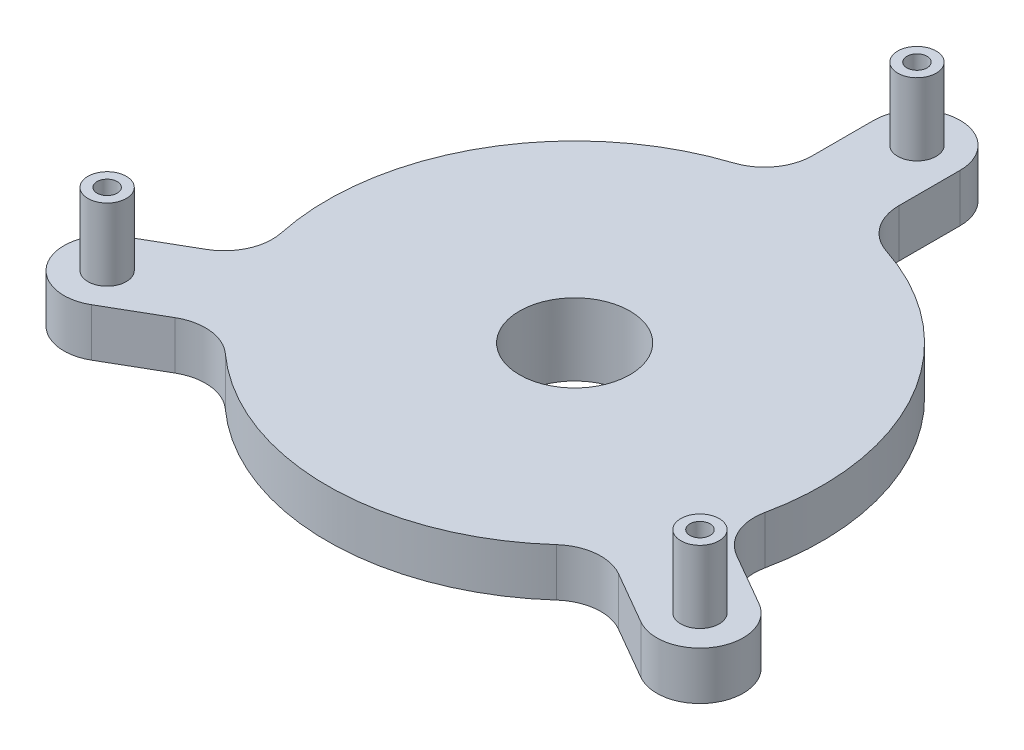
SolidWorks part; units mm, degrees
ref_plane "前基準面" through (0, 0, 0) normal (0, 0, 1) x (1, 0, 0)
ref_plane "上基準面" through (0, 0, 0) normal (0, 1, 0) x (1, 0, 0)
ref_plane "右基準面" through (0, 0, 0) normal (1, 0, 0) x (0, 0, -1)
sketch "草圖1" plane through (0, 0, 0) normal (0, 1, 0) x (1, 0, 0)
  circle A0 centre (0, 0) radius 82.5
  circle A1 centre (0, 0) radius 11.5
  dimension "D1" = 165
  dimension "D2" = 23
extrude "填料-伸長1" add sketch "草圖1" along normal blind 5
sketch "草圖2" plane through (0, 5, 0) normal (0, 1, 0) x (1, 0, 0)
  line L0 (0, 0) -> (0, 82.5) construction
  line L1 (0, 0) -> (71.4471, -41.25) construction
  line L2 (0, 0) -> (-71.4471, -41.25) construction
  circle A0 centre (0, 0) radius 82.5 construction
  circle A1 centre (0, 71.25) radius 4
  circle A2 centre (61.7043, -35.625) radius 4
  circle A3 centre (-61.7043, -35.625) radius 4
  circle A4 centre (0, 71.25) radius 2.1
  circle A5 centre (61.7043, -35.625) radius 2.1
  circle A6 centre (-61.7043, -35.625) radius 2.1
  point P15 (0, 0)
  point P22 (0, 0)
  dimension "D1" = 8
  dimension "D6" = 4.2
  dimension "D2" = 3
  dimension "D3" = 71.25
  dimension "D4" = 1.9
  dimension "D5" = 3
extrude "填料-伸長2" add sketch "草圖2" along normal blind 15
sketch "草圖3" plane through (0, 0, 0) normal (0, -1, 0) x (1, 0, 0)
  circle A0 centre (0, 0) radius 11.5 construction
  circle A1 centre (0, 0) radius 11.5
  circle A2 centre (0, 0) radius 34
  dimension "D2" = 68
  dimension "D1" = 22.5
extrude "填料-伸長3" add sketch "草圖3" along normal blind 5
sketch "草圖4" plane through (0, 5, 0) normal (0, 1, 0) x (1, 0, 0)
  line L0 (-9, 71.25) -> (-9, 58.4915)
  line L1 (9, 71.25) -> (9, 58.4915)
  line L2 (66.2043, -27.8308) -> (55.1551, -21.4515)
  line L3 (57.2043, -43.4192) -> (46.1551, -37.04)
  line L4 (-57.2043, -43.4192) -> (-46.1551, -37.04)
  line L5 (-66.2043, -27.8308) -> (-55.1551, -21.4515)
  circle A0 centre (0, 0) radius 51.5 construction
  arc A1 (-15.9106, 48.9806) -> (-50.3738, -10.7114) centre (0, 0) ccw
  circle A2 centre (-61.7043, -35.625) radius 9
  arc A3 (-66.2043, -27.8308) -> (-57.2043, -43.4192) centre (-61.7043, -35.625) ccw
  arc A4 (50.3738, -10.7114) -> (15.9106, 48.9806) centre (0, 0) ccw
  arc A5 (-46.1551, -37.04) -> (-34.4632, -38.2693) centre (-41.1551, -45.7002) cw
  arc A6 (46.1551, -37.04) -> (34.4632, -38.2693) centre (41.1551, -45.7002) ccw
  arc A7 (55.1551, -21.4515) -> (50.3738, -10.7114) centre (60.1551, -12.7912) cw
  arc A8 (9, 58.4915) -> (15.9106, 48.9806) centre (19, 58.4915) ccw
  arc A9 (-9, 58.4915) -> (-15.9106, 48.9806) centre (-19, 58.4915) cw
  arc A10 (-55.1551, -21.4515) -> (-50.3738, -10.7114) centre (-60.1551, -12.7912) ccw
  circle A11 centre (0, 71.25) radius 9
  arc A12 (9, 71.25) -> (-9, 71.25) centre (0, 71.25) ccw
  circle A13 centre (0, 0) radius 11.5 construction
  circle A14 centre (61.7043, -35.625) radius 9
  arc A15 (57.2043, -43.4192) -> (66.2043, -27.8308) centre (61.7043, -35.625) ccw
  circle A16 centre (0, 0) radius 11.5
  arc A17 (-34.4632, -38.2693) -> (34.4632, -38.2693) centre (0, 0) ccw
  circle A18 centre (0, 0) radius 82.5 construction
  circle A19 centre (0, 0) radius 82.5
  point P28 (0, 0)
  point P35 (-9, 50.7075)
  circle M24 centre (0, 0) radius 82.5
  dimension "D7" = 10
  dimension "D5" = 18
  dimension "D1" = 5
  dimension "D2" = 5
  dimension "D3" = 5
  dimension "D4" = 40
  dimension "D6" = 3
extrude "除料-伸長1" cut sketch "草圖4" against normal blind 10 and the other way through all contours A17 A5 L4 A3 L5 A10 A1 A9 L0 A12 L1 A8 A4 A7 L2 A15 L3 A6 M24 region at (-80.1665, 5, 0)
sketch "草圖5" plane through (0, 0, 0) normal (0, -1, 0) x (1, 0, 0)
  line L6 (-46.1551, 37.04) -> (-57.2043, 43.4192)
  line L7 (-66.2043, 27.8308) -> (-55.1551, 21.4515)
  line L8 (-9, -58.4915) -> (-9, -71.25)
  line L9 (9, -71.25) -> (9, -58.4915)
  line L10 (55.1551, 21.4515) -> (66.2043, 27.8308)
  line L11 (57.2043, 43.4192) -> (46.1551, 37.04)
  line L12 (-46.1551, 37.04) -> (-57.2043, 43.4192)
  line L13 (-66.2043, 27.8308) -> (-55.1551, 21.4515)
  line L14 (-9, -58.4915) -> (-9, -71.25)
  line L15 (9, -71.25) -> (9, -58.4915)
  line L16 (55.1551, 21.4515) -> (66.2043, 27.8308)
  line L17 (57.2043, 43.4192) -> (46.1551, 37.04)
  circle A0 centre (0, 0) radius 46
  arc A13 (34.4632, 38.2693) -> (-34.4632, 38.2693) centre (0, 0) ccw
  arc A14 (-46.1551, 37.04) -> (-34.4632, 38.2693) centre (-41.1551, 45.7002) ccw
  arc A15 (-57.2043, 43.4192) -> (-66.2043, 27.8308) centre (-61.7043, 35.625) ccw
  arc A16 (-50.3738, 10.7114) -> (-55.1551, 21.4515) centre (-60.1551, 12.7912) ccw
  arc A17 (-50.3738, 10.7114) -> (-15.9106, -48.9806) centre (0, 0) ccw
  arc A18 (-9, -58.4915) -> (-15.9106, -48.9806) centre (-19, -58.4915) ccw
  arc A19 (-9, -71.25) -> (9, -71.25) centre (0, -71.25) ccw
  arc A20 (15.9106, -48.9806) -> (9, -58.4915) centre (19, -58.4915) ccw
  arc A21 (15.9106, -48.9806) -> (50.3738, 10.7114) centre (0, 0) ccw
  arc A22 (55.1551, 21.4515) -> (50.3738, 10.7114) centre (60.1551, 12.7912) ccw
  arc A23 (66.2043, 27.8308) -> (57.2043, 43.4192) centre (61.7043, 35.625) ccw
  arc A24 (34.4632, 38.2693) -> (46.1551, 37.04) centre (41.1551, 45.7002) ccw
  arc A25 (34.4632, 38.2693) -> (-34.4632, 38.2693) centre (0, 0) ccw
  arc A26 (-46.1551, 37.04) -> (-34.4632, 38.2693) centre (-41.1551, 45.7002) ccw
  arc A27 (-57.2043, 43.4192) -> (-66.2043, 27.8308) centre (-61.7043, 35.625) ccw
  arc A28 (-50.3738, 10.7114) -> (-55.1551, 21.4515) centre (-60.1551, 12.7912) ccw
  arc A29 (-50.3738, 10.7114) -> (-15.9106, -48.9806) centre (0, 0) ccw
  arc A30 (-9, -58.4915) -> (-15.9106, -48.9806) centre (-19, -58.4915) ccw
  arc A31 (-9, -71.25) -> (9, -71.25) centre (0, -71.25) ccw
  arc A32 (15.9106, -48.9806) -> (9, -58.4915) centre (19, -58.4915) ccw
  arc A33 (15.9106, -48.9806) -> (50.3738, 10.7114) centre (0, 0) ccw
  arc A34 (55.1551, 21.4515) -> (50.3738, 10.7114) centre (60.1551, 12.7912) ccw
  arc A35 (66.2043, 27.8308) -> (57.2043, 43.4192) centre (61.7043, 35.625) ccw
  arc A36 (34.4632, 38.2693) -> (46.1551, 37.04) centre (41.1551, 45.7002) ccw
  dimension "D1" = 0
  dimension "D2" = 92
extrude "填料-伸長4" add sketch "草圖5" along normal up to surface (5 mm away) contours A25 A26 L12 A27 L13 A28 A29 A30 L14 A31 L15 A32 A33 A34 L16 A35 L17 A36 up to face at (0, -5, -34)
sketch "草圖6" plane through (0, 0, 0) normal (0, 1, 0) x (1, 0, 0)
  circle A1 centre (0, 0) radius 11.5
  circle A2 centre (0, 0) radius 11.5
  dimension "D1" = 0
extrude "除料-伸長2" cut sketch "草圖6" against normal through all
sketch "草圖7" plane through (0, -5, 0) normal (0, -1, 0) x (1, 0, 0)
  circle A0 centre (0, 0) radius 34.75
  circle A1 centre (0, 0) radius 11.5 construction
  circle A2 centre (0, 0) radius 11.5
  dimension "D1" = 69.5
extrude "填料-伸長5" add sketch "草圖7" along normal blind 5
